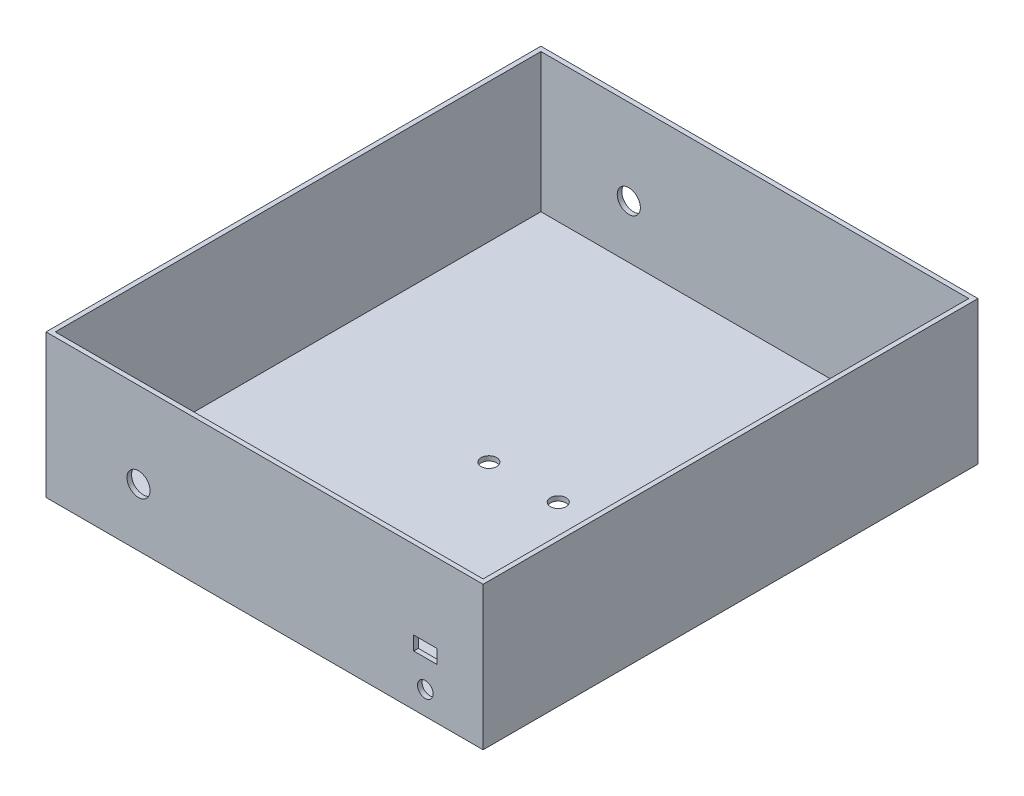
SolidWorks part; units mm, degrees
material "ABS"
ref_plane "Front Plane" through (0, 0, 0) normal (0, 0, 1) x (1, 0, 0)
ref_plane "Top Plane" through (0, 0, 0) normal (0, 1, 0) x (1, 0, 0)
ref_plane "Right Plane" through (0, 0, 0) normal (1, 0, 0) x (0, 0, -1)
sketch "Sketch2" plane through (0, 0, 0) normal (0, 1, 0) x (1, 0, 0)
  line L0 (-94.5, 107) -> (-94.5, -107)
  line L1 (-92.5, 105) -> (92.5, 105)
  line L2 (-92.5, 105) -> (-92.5, -105)
  line L3 (-92.5, -105) -> (92.5, -105)
  line L4 (92.5, 105) -> (92.5, -105)
  line L5 (-92.5, 105) -> (92.5, -105) construction
  line L6 (-92.5, -105) -> (92.5, 105) construction
  line L7 (-94.5, -107) -> (94.5, -107)
  line L8 (94.5, 107) -> (94.5, -107)
  line L9 (-94.5, 107) -> (94.5, 107)
  point P0 (0, 0)
  dimension "D1" = 210
  dimension "D2" = 185
  dimension "D3" = 2
extrude "Walls" add sketch "Sketch2" along normal blind 60
sketch "Sketch3" plane through (0, 0, 0) normal (0, -1, 0) x (1, 0, 0)
  line L1 (-94.5, -107) -> (94.5, -107)
  line L2 (-94.5, -107) -> (-94.5, 107)
  line L3 (-94.5, 107) -> (94.5, 107)
  line L4 (94.5, -107) -> (94.5, 107)
  line L5 (-94.5, -107) -> (94.5, 107) construction
  line L6 (-94.5, 107) -> (94.5, -107) construction
  point P0 (0, 0)
extrude "Base" add sketch "Sketch3" along normal blind 2
sketch "Sketch4" plane through (0, 0, -107) normal (0, 0, -1) x (-1, 0, 0)
  line L0 (94.5, -2) -> (-94.5, -2) construction
  line L3 (94.5, 60) -> (94.5, -2) construction
  line L4 (-74.5, 20) -> (-64.5, 20)
  line L5 (-74.5, 20) -> (-74.5, 26)
  line L6 (-74.5, 26) -> (-64.5, 26)
  line L7 (-64.5, 20) -> (-64.5, 26)
  line L8 (-74.5, 20) -> (-64.5, 26) construction
  line L9 (-74.5, 26) -> (-64.5, 20) construction
  line L10 (-94.5, 60) -> (-94.5, -2) construction
  circle A1 centre (54.5, 23) radius 5
  point P0 (-69.5, 23)
  point P1 (0, 0)
  point P14 (0, 0)
  dimension "D1" = 25
  dimension "D2" = 10
  dimension "D3" = 25
  dimension "D4" = 6
  dimension "D5" = 40
  dimension "D6" = 10
extrude "Cut-Extrude1" cut sketch "Sketch4" against normal through all
sketch "Sketch5" plane through (0, 0, -107) normal (0, 0, -1) x (-1, 0, 0)
  circle A0 centre (-69.5, 8.0963) radius 3.3782 construction
  circle A1 centre (-69.5, 8.0963) radius 3.3782
extrude "Cut-Extrude2" cut sketch "Sketch5" against normal through all
hole_wizard "1/4 Clearance Hole1" positions "Sketch7" profile "Sketch8" hole size "1/4" standard "ANSI Inch" end condition through all
sketch "Sketch7" plane through (0, -2, 0) normal (0, -1, 0) x (-1, 0, 0)
  line L0 (0, 0) -> (-94.5, 0) construction
  line L1 (-94.5, 107) -> (-94.5, -107) construction
  point P0 (-20, 0)
  point P2 (10, 0)
  point P18 (0, 0)
  point P19 (0, 0)
  dimension "D1" = 20
  dimension "D2" = 30
sketch "Sketch8" plane through (20, -2, 0) normal (1, 0, 0) x (0, 0, -1)
  line L0 (0, 0) -> (0, 62)
  line L1 (0, 62) -> (3.3782, 62)
  line L2 (3.3782, 62) -> (3.3782, 0)
  line L5 (3.3782, 0) -> (0, 0)
  line L11 (0, -6.35) -> (0, 107.95) construction
  dimension "Thru Hole Dia." = 6.7564
  dimension "Thru Hole Depth" = 62
